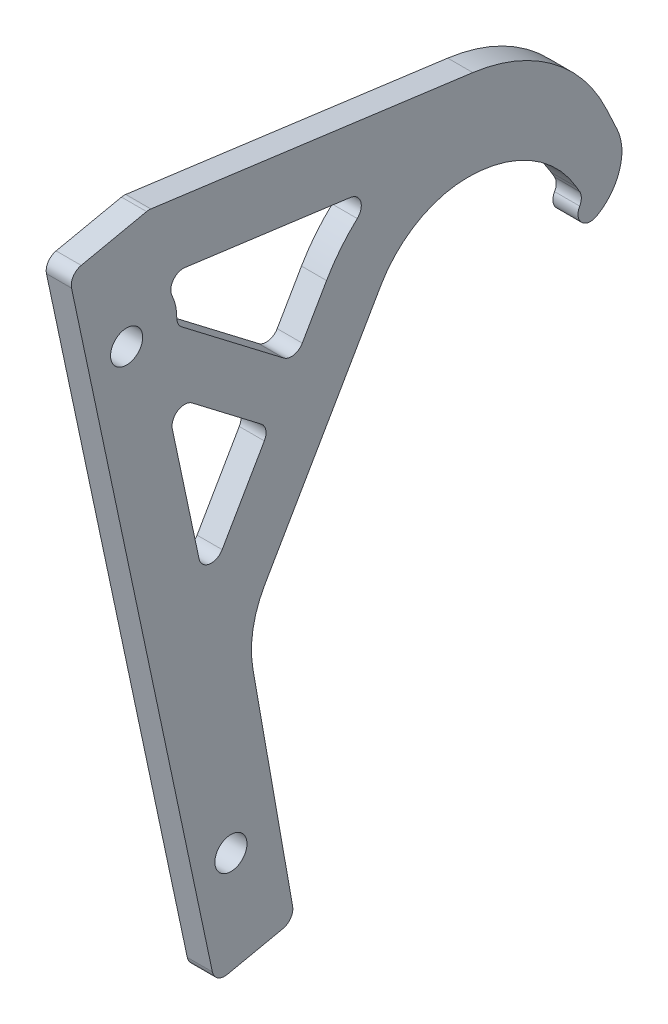
SolidWorks part; units mm, degrees
ref_plane "Front Plane" through (0, 0, 0) normal (0, 0, 1) x (1, 0, 0)
ref_plane "Top Plane" through (0, 0, 0) normal (0, 1, 0) x (1, 0, 0)
ref_plane "Right Plane" through (0, 0, 0) normal (1, 0, 0) x (0, 0, -1)
sketch "Sketch1" plane through (0, 0, 0) normal (1, 0, 0) x (0, 0, -1)
  line L0 (-25.9565, -2.286) -> (-10.9985, 23.622) construction
  line L1 (10.9985, 23.622) -> (25.9565, -2.286) construction
  line L2 (14.958, -21.336) -> (-14.958, -21.336) construction
  line L3 (0, 0) -> (0, 17.272) construction
  line L4 (0, 0) -> (14.958, -8.636) construction
  line L5 (0, 0) -> (-14.958, -8.636) construction
  line L6 (13.7482, 22.0345) -> (14.7391, 20.3181)
  line L7 (17.5167, 28.7321) -> (18.9067, 25.7514)
  line L8 (0, 17.272) -> (-2.2451, 19.5171) construction
  line L10 (-50.4755, 44.45) -> (-31.9922, -42.5073)
  line L11 (-31.9922, -42.5073) -> (-21.8989, -40.3619)
  line L12 (-21.8989, -40.3619) -> (-27.9913, -5.8103)
  line L13 (-27.9913, -5.8103) -> (-10.9985, 23.622)
  line L14 (-37.3282, -17.4031) -> (-25.9565, -14.986) construction
  line L15 (-50.4755, 44.45) -> (-40.3823, 46.5954)
  line L16 (-40.3823, 46.5954) -> (0.6345, 41.1308)
  arc A0 (-10.9985, 23.622) -> (10.9985, 23.622) centre (0, 17.272) cw construction
  arc A1 (25.9565, -2.286) -> (14.958, -21.336) centre (14.958, -8.636) cw construction
  arc A2 (-14.958, -21.336) -> (-25.9565, -2.286) centre (-14.958, -8.636) cw construction
  arc A3 (0, 29.972) -> (13.7482, 22.0345) centre (0, 14.097) cw
  arc A4 (0, 29.972) -> (-10.9985, 23.622) centre (0, 17.272) ccw
  arc A5 (14.7391, 20.3181) -> (16.3266, 17.5685) centre (15.5329, 18.9433) ccw
  arc A6 (16.3266, 17.5685) -> (18.9067, 25.7514) centre (13.1516, 23.0677) ccw
  arc A7 (0.6345, 41.1308) -> (17.5167, 28.7321) centre (-2.2451, 19.5171) cw
  point P13 (0, 29.972)
  point P23 (0, 0)
  dimension "D1" = 12.7
  dimension "D3" = 1.5875
  dimension "D4" = 6.35
  dimension "D2" = 51.308
  dimension "D5" = 5
  dimension "D6" = 3.175
  dimension "D7" = 12
  dimension "D8" = 28.575
  dimension "D9" = 10.3187
  dimension "D10" = 88.9
  dimension "D11" = 44.45
  dimension "D12" = 45
  dimension "D13" = 19.05
  dimension "D14" = 2
extrude "Boss-Extrude1" add sketch "Sketch1" along normal blind 3.175
fillet "Fillet1" radius 12.7 1 edges at (1.5875, -5.8103, 27.9913)
fillet "Fillet2" radius 1.5875 4 edges at (1.5875, -42.5073, 31.9922) (1.5875, -40.3619, 21.8989) (1.5875, 44.45, 50.4755) (1.5875, 46.5954, 40.3823)
fillet "Fillet3" radius 1.5875 1 edges at (1.5875, 20.3181, -14.7391)
sketch "Sketch2" plane through (3.175, 0, 0) normal (1, 0, 0) x (0, 0, -1)
  line L7 (-29.9742, -29.0947) -> (-43.1766, 33.0177) construction
  line L8 (-50.1455, 42.8972) -> (-32.3222, -40.9545) construction
  line L9 (-30.4394, -42.1773) -> (-23.3984, -40.6807) construction
  line L10 (-43.1766, 33.0177) -> (0, 0) construction
  line L24 (-21.8483, 20.7046) -> (-17.8726, 27.5907)
  line L26 (-36.8796, 32.1992) -> (-21.8483, 20.7046)
  line L27 (-38.2862, 25.281) -> (-25.05, 15.1591)
  line L28 (-38.2862, 25.281) -> (-33.1404, 1.0719)
  line L29 (-41.248, 35.5398) -> (1.9287, 2.5221) construction
  line L31 (-50.1455, 42.8972) -> (-32.3222, -40.9545) construction
  line L33 (-11.0788, 34.6837) -> (-40.0723, 38.5465)
  line L34 (-40.0723, 38.5465) -> (-41.0612, 38.3363)
  line L35 (-41.0612, 38.3363) -> (-33.1404, 1.0719)
  line L36 (-32.5542, 2.1615) -> (-17.8726, 27.5907)
  line L37 (-11.0788, 34.6837) -> (-40.0474, 38.5431)
  line L40 (-32.5542, 2.1615) -> (-25.05, 15.1591)
  circle A10 centre (-43.1766, 33.0177) radius 2.032
  circle A11 centre (-29.9742, -29.0947) radius 2.032
  arc A31 (-36.8796, 32.1992) -> (-40.0474, 38.5431) centre (-43.1766, 33.0177) ccw
  arc A41 (-11.0788, 34.6837) -> (-17.8726, 27.5907) centre (0, 17.272) ccw
  arc A42 (-32.5542, 2.1615) -> (-33.1404, 1.0719) centre (-14.6816, -8.1572) ccw
  arc A43 (-11.0788, 34.6837) -> (-17.8726, 27.5907) centre (0, 17.272) ccw
  arc A44 (-32.5542, 2.1615) -> (-33.1404, 1.0719) centre (-14.6816, -8.1572) ccw
  point P8 (-34.1784, -1.391)
  dimension "D3" = 4.064
  dimension "D6" = 6.35
  dimension "D2" = 4.7625
  dimension "D4" = 63.5
  dimension "D5" = 12.7
  dimension "D7" = 6.35
  dimension "D9" = 7.9375
  dimension "D1" = 7.9375
  dimension "D8" = 3.175
extrude "Cut-Extrude1" cut sketch "Sketch2" against normal through all
fillet "Fillet4" radius 1.5875 7 edges at (1.5875, 20.7046, 21.8483) (1.5875, 34.6837, 11.0788) (1.5875, 38.5431, 40.0474) (1.5875, 32.1992, 36.8796) (1.5875, 25.281, 38.2862) (1.5875, 1.0719, 33.1404) (1.5875, 15.1591, 25.05)
